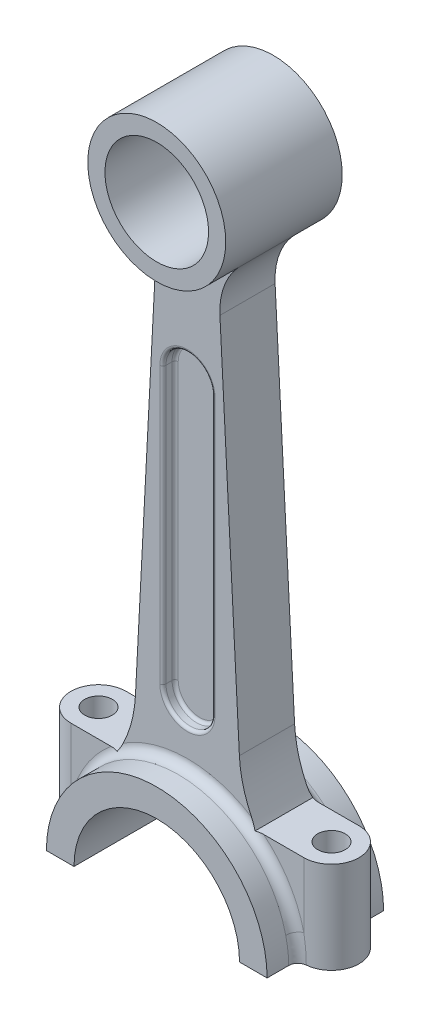
SolidWorks part; units mm, degrees
ref_plane "Front Plane" through (0, 0, 0) normal (0, 0, 1) x (1, 0, 0)
ref_plane "Top Plane" through (0, 0, 0) normal (0, 1, 0) x (1, 0, 0)
ref_plane "Right Plane" through (0, 0, 0) normal (1, 0, 0) x (0, 0, -1)
sketch "Sketch1" plane through (0, 0, 0) normal (0, 0, 1) x (1, 0, 0)
  line L0 (0, 0) -> (0, -174.2) construction
  line L1 (-10, -20.1556) -> (-17.8497, -169.9368)
  line L2 (10, -20.1556) -> (17.8497, -169.9368)
  line L3 (-36, -201.2) -> (-27, -201.2)
  line L4 (27, -201.2) -> (36, -201.2)
  circle A0 centre (0, 0) radius 22.5
  circle A1 centre (0, 0) radius 16.9
  arc A2 (36, -201.2) -> (-36, -201.2) centre (0, -201.2) ccw
  arc A3 (27, -201.2) -> (-27, -201.2) centre (0, -201.2) ccw
  dimension "D1" = 45
  dimension "D2" = 33.8
  dimension "D3" = 72
  dimension "D4" = 54
  dimension "D5" = 201.2
  dimension "D6" = 20
  dimension "D7" = 6
extrude "Boss-Extrude2" add sketch "Sketch1" along normal mid plane 38 contours A1 A0 | A2 A3 | L3 A3 L4 A2 region at (-11.5231, 18.5805, 0) region at (0, -166.005, 0)
extrude "Boss-Extrude3" add sketch "Sketch1<4>" along normal mid plane 18 contours L0 A0 L1 A2 | A0 L0 A2 L2 region at (7.1843, -100.8455, 0) region at (-7.1843, -100.8455, 0)
sketch "Sketch1<4>" plane through (0, 0, 0) normal (0, 0, 1) x (1, 0, 0) same geometry as "Sketch1"
sketch "Sketch2" plane through (0, 0, 9) normal (0, 0, 1) x (1, 0, 0)
  line L0 (0, 0) -> (0, -201.2) construction
  line L1 (0, -145.6) -> (0, -55.6) construction
  line L2 (-8, -145.6) -> (-8, -55.6)
  line L3 (8, -145.6) -> (8, -55.6)
  arc A0 (-8, -145.6) -> (8, -145.6) centre (0, -145.6) ccw
  arc A1 (8, -55.6) -> (-8, -55.6) centre (0, -55.6) ccw
  point P6 (0, -100.6)
  dimension "D2" = 8
  dimension "D1" = 90
extrude "Cut-Extrude1" cut sketch "Sketch2" against normal blind 4 and the other way through all
mirror "Mirror1" about plane through (0, 0, 0) normal (0, 0, 1) of "Cut-Extrude1"
fillet "Fillet1" radius 1 16 edges at (0, -47.6, -9) (8, -100.6, -9) (-8, -100.6, 5) (0, -47.6, 5) (8, -100.6, 5) (0, -153.6, 5) (8, -100.6, -5) (0, -47.6, -5) (-8, -100.6, -5) (0, -153.6, -5) (-8, -100.6, -9) (0, -153.6, -9) (0, -47.6, 9) (8, -100.6, 9) (-8, -100.6, 9) (0, -153.6, 9)
fillet "Fillet4" radius 40 2 edges at (17.8497, -169.9368, 0) (-17.8497, -169.9368, 0)
fillet "Fillet5" radius 22.5 2 edges at (10, -20.1556, 0) (-10, -20.1556, 0)
ref_plane "Plane2" through (0, -171.2, 0) normal (0, -1, 0) x (-1, 0, 0)
sketch "Sketch6" plane through (0, -171.2, 0) normal (0, -1, 0) x (-1, 0, 0)
  line L0 (38, 0) -> (-38, 0) construction
  line L1 (38, -9) -> (-38, -9)
  line L2 (38, 9) -> (-38, 9)
  arc A0 (38, -9) -> (38, 9) centre (38, 0) ccw
  arc A1 (-38, 9) -> (-38, -9) centre (-38, 0) ccw
  point P2 (0, 0)
  dimension "D2" = 9
  dimension "D1" = 76
extrude "Boss-Extrude5" add sketch "Sketch6" along normal up to surface (30 mm away) up to face at (31.5, -201.2, 0)
sketch "Sketch9" plane through (0, 0, -9) normal (0, 0, -1) x (-1, 0, 0)
  line L0 (-27, -201.2) -> (27, -201.2) construction
  line L1 (-27, -201.2) -> (27, -201.2)
  arc A0 (-27, -201.2) -> (27, -201.2) centre (0, -201.2) cw
  arc A1 (27, -201.2) -> (-27, -201.2) centre (0, -201.2) ccw construction
extrude "Cut-Extrude2" cut sketch "Sketch9" against normal through all
sketch "Sketch10" plane through (0, -171.2, 0) normal (0, 1, 0) x (1, 0, 0)
  circle A0 centre (-38, 0) radius 4.5
  circle A1 centre (38, 0) radius 4.5
  dimension "D1" = 9
  dimension "D2" = 9
extrude "Cut-Extrude3" cut sketch "Sketch10" against normal through all
fillet "Fillet6" radius 3 2 edges at (0, -165.2, 9) (0, -165.2, -9)
